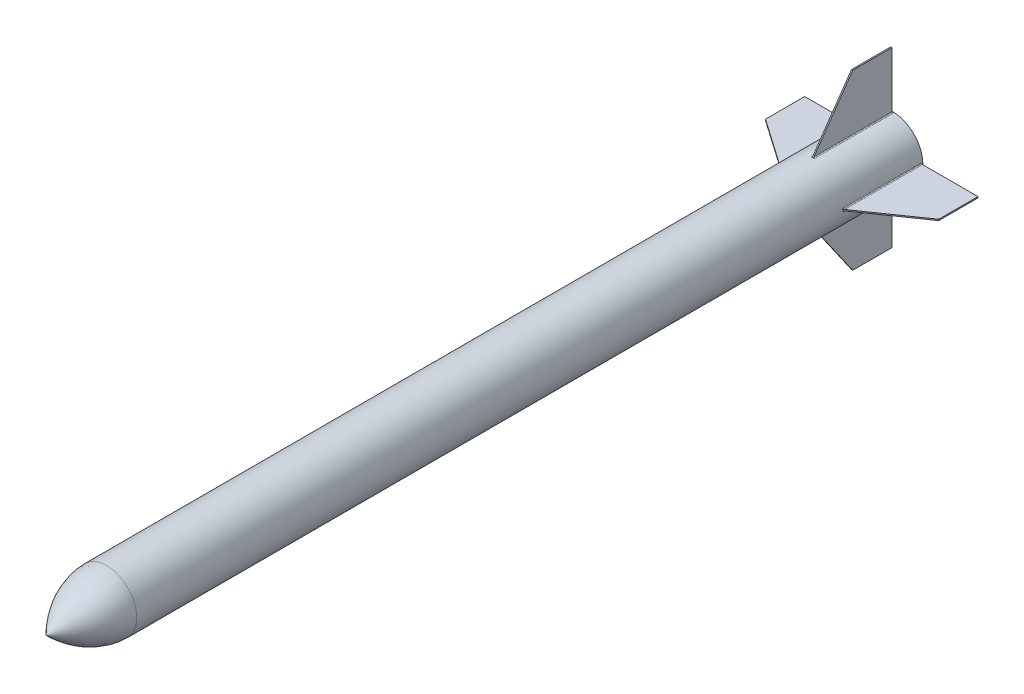
SolidWorks part; units mm, degrees
ref_plane "Front Plane" through (0, 0, 0) normal (0, 0, 1) x (1, 0, 0)
ref_plane "Top Plane" through (0, 0, 0) normal (0, 1, 0) x (1, 0, 0)
ref_plane "Right Plane" through (0, 0, 0) normal (1, 0, 0) x (0, 0, -1)
sketch "Sketch2" plane through (0, 0, 0) normal (1, 0, 0) x (0, 0, -1)
  line L0 (161.2004, 77.7716) -> (2196.6929, 77.7716)
  line L1 (2196.6929, 77.7716) -> (2196.6929, -0.5514)
  line L2 (2196.6929, -0.5514) -> (4.4824, -0.5514)
  line L3 (4.4824, -0.5514) -> (-152.2356, -0.5514) construction
  line L4 (4.4824, -0.5514) -> (2.1037, 77.7716) construction
  spline S0 degree 2 poles (-8.0267, -13.5537) (84.4228, 86.229) (176.8722, 76.9883) knots 0 0 0 1 1 1 construction
  spline S1 degree 2 poles (4.4824, -0.5514) (82.8414, 77.7716) (161.2004, 77.7716) knots 0.067654 0.067654 0.067654 0.915241 0.915241 0.915241
  dimension "D1" = 2035.4925
  dimension "D2" = 156.718
  dimension "D3" = 78.3229
revolve "Revolve1" add sketch "Sketch2" angle 360 about L2
sketch "Sketch3" plane through (0, 0, -2196.6929) normal (0, 0, -1) x (-1, 0, 0)
  circle A0 centre (0, 0) radius 43.942
  dimension "D1" = 87.884
extrude "Boss-Extrude1" add sketch "Sketch3" along normal blind 15.24
ref_plane "Plane1" through (0, 254, 0) normal (0, 1, 0) x (1, 0, 0)
sketch "Sketch4" plane through (0, 254, 0) normal (0, 1, 0) x (1, 0, 0)
  line L1 (-1.5875, 1990.3179) -> (1.5875, 1990.3179)
  line L2 (-1.5875, 1990.3179) -> (-1.5875, 2193.5179)
  line L3 (-1.5875, 2193.5179) -> (1.5875, 2193.5179)
  line L4 (1.5875, 1990.3179) -> (1.5875, 2193.5179)
  line L5 (78.3229, 2196.6929) -> (-78.3229, 2196.6929) construction
  point P6 (0, 2193.5179)
  dimension "D1" = 3.175
  dimension "D2" = 3.175
  dimension "D3" = 203.2
extrude "Boss-Extrude2" add sketch "Sketch4" against normal up to surface (176.2445 mm away) up to face at (0, 77.7716, -161.2004)
sketch "Sketch5" plane through (-1.5875, 0, 0) normal (-1, 0, 0) x (0, 0, 1)
  line L0 (-2193.5179, 223.8055) -> (-2091.9179, 223.8055)
  line L1 (-2193.5179, 77.7555) -> (-2193.5179, 254) construction
  line L2 (-2091.9179, 223.8055) -> (-1990.3179, 77.7555)
  line L3 (-1990.3179, 77.7555) -> (-1990.3179, 254)
  line L4 (-1990.3179, 254) -> (-2193.5179, 254)
  line L5 (-2193.5179, 254) -> (-2193.5179, 223.8055)
  dimension "D1" = 101.6
  dimension "D2" = 146.05
extrude "Cut-Extrude1" cut sketch "Sketch5" against normal up to next
fillet "Fillet1" radius 2.54 2 edges at (1.5875, 77.7555, -2091.9179) (-1.5875, 77.7555, -2091.9179)
pattern_circular "CirPattern1" count 4 over 360 about axis through (0, -0.5514, -2196.6929) along (0, 0, -1) of "Cut-Extrude1", "Fillet1", "Boss-Extrude2"
equation "\"Body Tube Length\" = 80.1375"
equation "\"D1@Sketch2\"=\"Body Tube Length\""
equation "\"Retainer Diameter\" = 3.46"
equation "\"D1@Sketch3\"=\"Retainer Diameter\""
equation "\"Retainer Height\" = 0.6"
equation "\"D1@Boss-Extrude1\"=\"Retainer Height\""
equation "\"Fin Offset\" = .125"
equation "\"D1@Sketch4\"=\"Fin Offset\""
equation "\"Fin Thickness\" = .125"
equation "\"D2@Sketch4\"=\"Fin Thickness\""
equation "\"Fin Root Chord\"= 8"
equation "\"D3@Sketch4\"=\"Fin Root Chord\""
equation "\"Fin Tip Chord\"= 4"
equation "\"D1@Sketch5\"=\"Fin Tip Chord\""
equation "\"Fin Height\"= 5.75"
equation "\"D2@Sketch5\"=\"Fin Height\""
equation "\"Fin Epoxy Fillet Radius\"=0.1"
equation "\"D1@Fillet1\"=\"Fin Epoxy Fillet Radius\""
equation "\"Nosecone Length\"= 6.17"
equation "\"D2@Sketch2\"=\"Nosecone Length\""
equation "\"Rocket Radius\"=3.08358"
equation "\"D3@Sketch2\"= \"Rocket Radius\""
